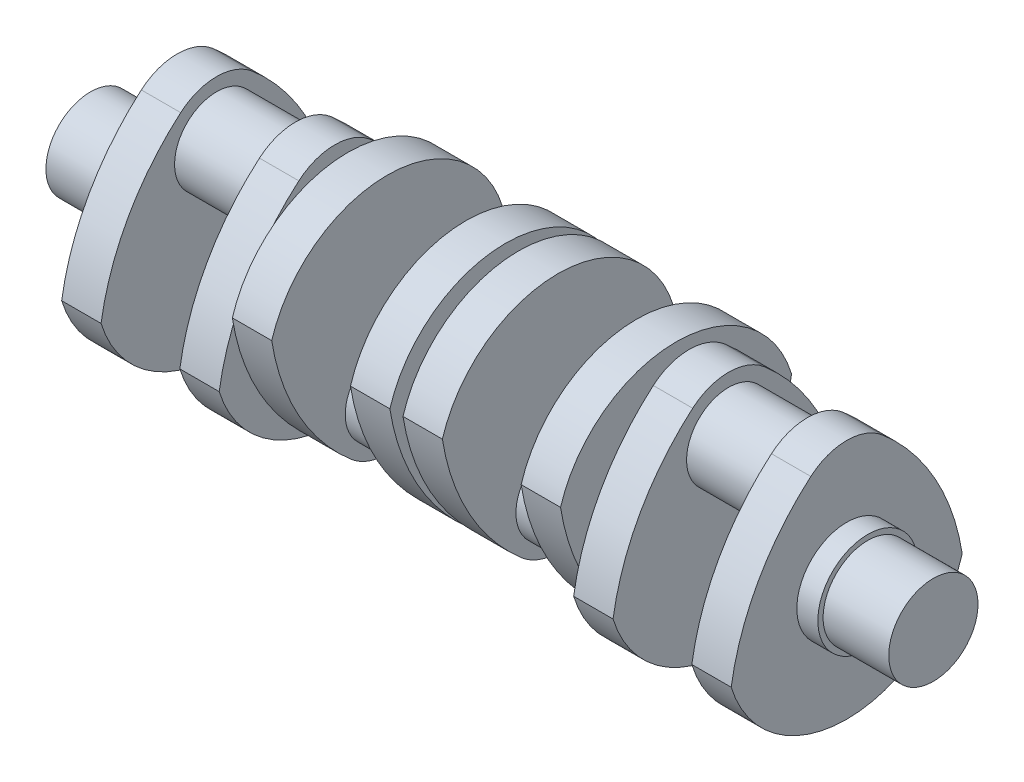
SolidWorks part; units mm, degrees
ref_plane "Front Plane" through (0, 0, 0) normal (0, 0, 1) x (1, 0, 0)
ref_plane "Top Plane" through (0, 0, 0) normal (0, 1, 0) x (1, 0, 0)
ref_plane "Right Plane" through (0, 0, 0) normal (1, 0, 0) x (0, 0, -1)
sketch "Sketch1" plane through (0, 0, 0) normal (1, 0, 0) x (0, 0, -1)
  circle A0 centre (0, 0) radius 19
  circle A1 centre (0, 0) radius 17
  dimension "D1" = 38
  dimension "D2" = 34
extrude "Boss-Extrude1" add sketch "Sketch1" against normal blind 25 contours A1
extrude "Boss-Extrude2" add sketch "Sketch1<3>" along normal blind 8 contours A0
sketch "Sketch1<3>" plane through (0, 0, 0) normal (1, 0, 0) x (0, 0, -1) same geometry as "Sketch1"
sketch "Sketch2" plane through (8, 0, 0) normal (1, 0, 0) x (0, 0, -1)
  line L0 (0, 0) -> (0, 38.1352) construction
  arc A1 (-44, -13.4164) -> (44, -13.4164) centre (0, 0) ccw
  arc A3 (13.6681, 40.9431) -> (44, -13.4164) centre (-44.9095, -27.3845) cw
  arc A5 (-13.6681, 40.9431) -> (-44, -13.4164) centre (44.9095, -27.3845) ccw
  arc A6 (-13.6681, 40.9431) -> (13.6681, 40.9431) centre (0, 25) cw
  point P10 (0, -46)
  point P11 (0, 0)
  dimension "D1" = 90
  dimension "D3" = 46
  dimension "D4" = 25
  dimension "D5" = 21
  dimension "D2" = 88
extrude "Boss-Extrude3" add sketch "Sketch2" along normal blind 15
sketch "Sketch3" plane through (23, 0, 0) normal (1, 0, 0) x (0, 0, -1)
  circle A0 centre (0, 25) radius 16
  point P3 (0, 0)
  dimension "D1" = 32
extrude "Boss-Extrude4" add sketch "Sketch3" along normal blind 15
mirror "Mirror1" about plane through (38, 25, 0) normal (1, 0, 0) of "Boss-Extrude4", "Boss-Extrude3"
sketch "Sketch4" plane through (68, 0, 0) normal (1, 0, 0) x (0, 0, -1)
  circle A0 centre (0, 0) radius 17
  dimension "D1" = 34
extrude "Boss-Extrude5" add sketch "Sketch4" along normal blind 5
sketch "Sketch5" plane through (73, 0, 0) normal (1, 0, 0) x (0, 0, -1)
  circle A0 centre (0, 0) radius 17 construction
  arc A8 (44, 13.4164) -> (-44, 13.4164) centre (0, 0) ccw
  arc A9 (-44, 13.4164) -> (-13.6681, -40.9431) centre (44.9095, 27.3845) ccw
  arc A10 (-13.6681, -40.9431) -> (13.6681, -40.9431) centre (0, -25) ccw
  arc A11 (13.6681, -40.9431) -> (44, 13.4164) centre (-44.9095, 27.3845) ccw
  dimension "D1" = 46
  dimension "D2" = 90
  dimension "D3" = 21
  dimension "D4" = 13.6681
  dimension "D5" = 44
extrude "Boss-Extrude6" add sketch "Sketch5" along normal blind 15
sketch "Sketch6" plane through (88, 0, 0) normal (1, 0, 0) x (0, 0, -1)
  circle A0 centre (0, -25) radius 16
  dimension "D1" = 32
extrude "Boss-Extrude7" add sketch "Sketch6" along normal blind 30
sketch "Sketch7" plane through (118, 0, 0) normal (1, 0, 0) x (0, 0, -1)
  arc A4 (44, 13.4164) -> (-44, 13.4164) centre (0, 0) ccw
  arc A5 (-44, 13.4164) -> (-13.6681, -40.9431) centre (44.9095, 27.3845) ccw
  arc A6 (-13.6681, -40.9431) -> (13.6681, -40.9431) centre (0, -25) ccw
  arc A7 (13.6681, -40.9431) -> (44, 13.4164) centre (-44.9095, 27.3845) ccw
  arc A8 (44, 13.4164) -> (-44, 13.4164) centre (0, 0) ccw
  arc A9 (-44, 13.4164) -> (-13.6681, -40.9431) centre (44.9095, 27.3845) ccw
  arc A10 (-13.6681, -40.9431) -> (13.6681, -40.9431) centre (0, -25) ccw
  arc A11 (13.6681, -40.9431) -> (44, 13.4164) centre (-44.9095, 27.3845) ccw
  dimension "D1" = 0
extrude "Boss-Extrude8" add sketch "Sketch7" along normal blind 15
sketch "Sketch8" plane through (133, 0, 0) normal (1, 0, 0) x (0, 0, -1)
  circle A0 centre (0, 0) radius 17
  dimension "D1" = 34
extrude "Boss-Extrude9" add sketch "Sketch8" along normal blind 2.5
mirror "Mirror12" about plane through (135.5, 0, 0) normal (1, 0, 0) of bodies 110
